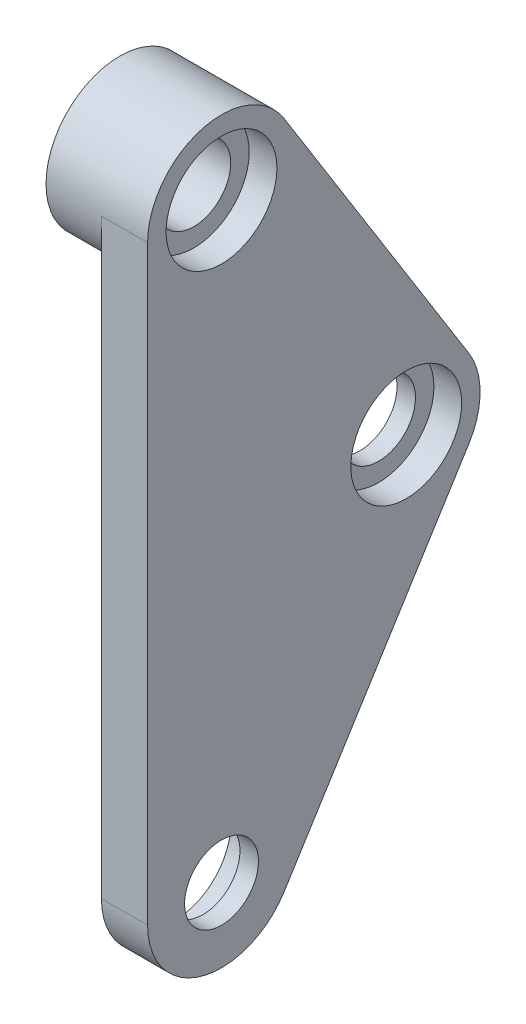
SolidWorks part; units mm, degrees
ref_plane "前视基准面" through (0, 0, 0) normal (0, 0, 1) x (1, 0, 0)
ref_plane "上视基准面" through (0, 0, 0) normal (0, 1, 0) x (1, 0, 0)
ref_plane "右视基准面" through (0, 0, 0) normal (1, 0, 0) x (0, 0, -1)
other "Configuration Table"
sketch "草图1" plane through (0, 0, 0) normal (1, 0, 0) x (0, 0, -1)
  line L0 (0, -20) -> (18, -20) construction
  line L1 (0, 0) -> (18, 0) construction
  line L2 (0, 0) -> (0, -40)
  line L3 (0, -40) -> (18, -40) construction
  line L4 (18, 0) -> (18, -40) construction
  line L5 (7.392, -1.88) -> (17.392, -17.88)
  line L6 (17.392, -22.12) -> (7.392, -38.12)
  circle A0 centre (4, -4) radius 4
  circle A1 centre (4, -36) radius 4
  circle A2 centre (14, -20) radius 4
  circle A3 centre (4, -4) radius 2
  circle A4 centre (14, -20) radius 2
  circle A5 centre (4, -36) radius 2
  dimension "D1" = 8
  dimension "D2" = 4
  dimension "D3" = 40
  dimension "D4" = 18
extrude "凸台-拉伸1" add sketch "草图1" along normal blind 2.5 contours A2 L5 A0 L2 A1 L6 | A0 | A2 | A1 region at (0, -20, -6.5849)
extrude "凸台-拉伸2" add sketch "草图1<4>" against normal blind 3 contours A0
sketch "草图1<4>" plane through (0, 0, 0) normal (1, 0, 0) x (0, 0, -1) same geometry as "草图1"
extrude "切除-拉伸1" cut sketch "草图1<3>" along normal through all both and the other way through all contours A3 | A4 | A5
sketch "草图1<3>" plane through (0, 0, 0) normal (1, 0, 0) x (0, 0, -1) same geometry as "草图1"
sketch "草图2" plane through (2.5, 0, 0) normal (1, 0, 0) x (0, 0, -1)
  circle A0 centre (4, -4) radius 3
  circle A1 centre (14, -20) radius 3
  circle A2 centre (4, -36) radius 3
  circle M3 centre (4, -4) radius 2
  arc M9 (7.392, -1.88) -> (0, -4) centre (4, -4) ccw
  dimension "D1" = 6
extrude "切除-拉伸2" cut sketch "草图2" against normal blind 1.5 contours A0 M9 M3 | A1 region at (2.5, -4, -1.0849)
extrude "切除-拉伸3" cut sketch "草图2<3>" along normal blind 1.5 from surface contours A2 starting at face at (0, -20, -16)
sketch "草图2<3>" plane through (2.5, 0, 0) normal (1, 0, 0) x (0, 0, -1) same geometry as "草图2"
ref_plane "基准面1" through (3.5, 0, 0) normal (1, 0, 0) x (0, 0, -1)
mirror "镜向2" about plane through (3.5, 0, 0) normal (1, 0, 0) of bodies 111 109
sketch "草图3" plane through (0, 0, 0) normal (0, 0, 1) x (1, 0, 0)
  line L1 (-4.5571, 5.5451) -> (3.4263, 5.5451)
  line L2 (-4.5571, 5.5451) -> (-4.5571, -46.6048)
  line L3 (-4.5571, -46.6048) -> (3.4263, -46.6048)
  line L4 (3.4263, 5.5451) -> (3.4263, -46.6048)
extrude "切除-拉伸4" cut sketch "草图3" against normal through all flip side to cut contours L2 L3 L4 L1
